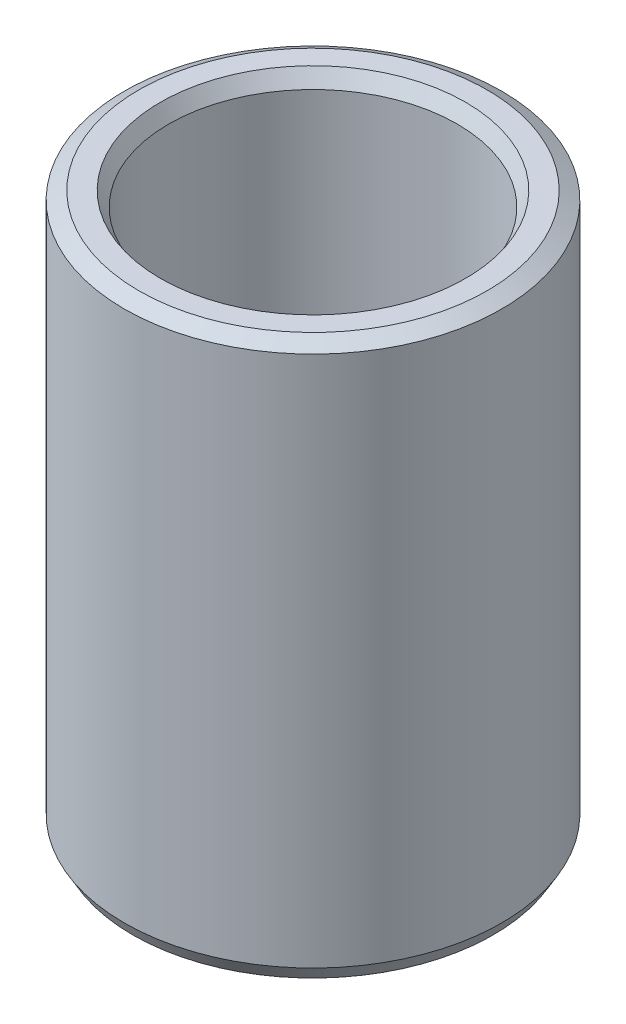
SolidWorks part; units mm, degrees
ref_plane "Front Plane" through (0, 0, 0) normal (0, 0, 1) x (1, 0, 0)
ref_plane "Top Plane" through (0, 0, 0) normal (0, 1, 0) x (1, 0, 0)
ref_plane "Right Plane" through (0, 0, 0) normal (1, 0, 0) x (0, 0, -1)
sketch "Sketch1" plane through (0, 0, 0) normal (0, 1, 0) x (1, 0, 0)
  circle A0 centre (0, 0) radius 25
  dimension "SLEEVE_OD" = 50
extrude "Boss-Extrude1" add sketch "Sketch1" along normal blind 73.4862
sketch "Sketch2" plane through (0, 0, 0) normal (0, 1, 0) x (1, 0, 0)
  circle A0 centre (0, 0) radius 19.0989
  dimension "BORE_D" = 38.1977
extrude "Cut-Extrude1" cut sketch "Sketch2" along normal through all
chamfer "Chamfer1" distance 1.1183 angle 60 4 edges at (0, 73.4862, 19.0989) (0, 0, 19.0989) (0, 0, 25) (0, 73.4862, 25) first distance on face at (0, 73.4862, 19.0989) first distance on face at (0, 0, 19.0989) first distance on face at (0, 73.4862, 25)
